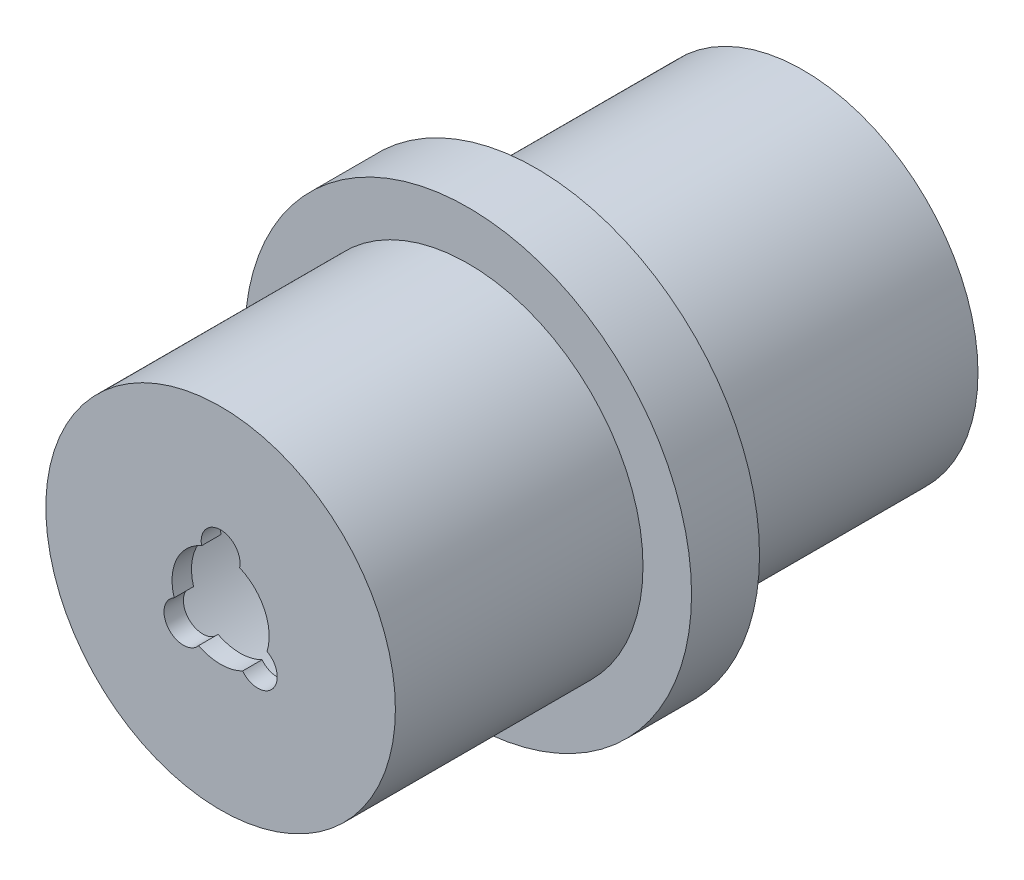
SolidWorks part; units mm, degrees
ref_plane "Front Plane" through (0, 0, 0) normal (0, 0, 1) x (1, 0, 0)
ref_plane "Top Plane" through (0, 0, 0) normal (0, 1, 0) x (1, 0, 0)
ref_plane "Right Plane" through (0, 0, 0) normal (1, 0, 0) x (0, 0, -1)
sketch "Sketch1" plane through (0, 0, 0) normal (1, 0, 0) x (0, 0, -1)
  line L0 (-60, 5) -> (-58, 5)
  line L1 (-60, 0) -> (0, 0)
  line L2 (-60, 0) -> (-60, 23)
  line L3 (-60, 23) -> (0, 23)
  line L4 (0, 0) -> (0, 23)
  line L5 (-1072.3815, 0) -> (1072.3815, 0) construction
  line L6 (-31, -974.342) -> (-31, 49025.6579)
  line L10 (-58, 0) -> (-2, 0)
  line L11 (-58, 0) -> (-58, 17)
  line L12 (-58, 17) -> (-2, 17)
  line L13 (-2, 0) -> (-2, 17)
  line L15 (-60, 18) -> (0, 18)
  line L16 (-27.5, 23) -> (-27.5, 18)
  line L17 (-2, 13) -> (0, 13)
  line L18 (-34.5, 23) -> (-34.5, 18)
  point P14 (-31, 17)
  dimension "D3" = 56
  dimension "D1" = 2
  dimension "D2" = 17
  dimension "D6" = 27
  dimension "D5" = 5
  dimension "D9" = 4
  dimension "D4" = 6
  dimension "D7" = 2
  dimension "D8" = 1
  dimension "D10" = 7
revolve "Revolve1" add sketch "Sketch1" angle 360 about L5 region at (0, 11.5, 59.6822) region at (0, 20.5, 32.75) region at (0, 17.5, 30.686) region at (0, 20.5, 29.25)
ref_axis "Axis1" through (0, 0, -68.4732) along (0, 0, 1)
ref_axis "Axis2" through (0, -974.342, 31) along (0, 1, 0)
ref_plane "Plane1" through (0, 0, 31) normal (0, 0, 1) x (1, 0, 0)
sketch "Sketch3" plane through (0, 0, 31) normal (0, 0, 1) x (1, 0, 0)
  line L0 (0, -999.5695) -> (0, 49000.4305) construction
  line L1 (-340.1578, -934.5758) -> (16760.8494, 46050.0552) construction
  line L2 (-1, 19.9725) -> (1, 19.9725)
  line L3 (338.8634, -931.0195) -> (-16762.1438, 46053.6116) construction
  line L4 (1, 19.9725) -> (4.5052, 16.5181) construction
  line L5 (0, 19.9725) -> (0, 23.1006) construction
  line L6 (2.0302, 19.9725) -> (-0.0328, 19.9725) construction
  line L7 (3.5107, 17.4982) -> (0.2868, 20.6753) construction
  line L8 (1, 19.9725) -> (1.1001, 21.9725) construction
  line L9 (4.5052, 16.5181) -> (4.684, 16.342)
  line L10 (6.4984, 17.8542) -> (7.5244, 20.6732)
  line L11 (-6.4984, 17.8542) -> (-7.5244, 20.6732)
  line L12 (-4.5052, 16.5181) -> (-4.684, 16.342)
  circle A4 centre (0, 0) radius 17 construction
  circle A6 centre (0, 0) radius 17
  circle A8 centre (5.2072, 17.2304) radius 1 construction
  arc A10 (6.4984, 17.8542) -> (-6.4984, 17.8542) centre (0, 0) cw
  circle A13 centre (0, 0) radius 22
  spline S0 degree 3 poles (1, 19.9725) (1.8375, 19.9725) (3.4007, 17.6066) (4.5052, 16.5181) knots 0 0 0 0 1 1 1 1
  spline S1 degree 3 poles (-1, 19.9725) (-1.8375, 19.9725) (-3.4007, 17.6066) (-4.5052, 16.5181) knots 0 0 0 0 1 1 1 1
  point P11 (0, 19.9725)
  point P13 (5.8143, 15.9748)
  point P16 (0, 22)
  point P20 (0, 19.9725)
  dimension "D2" = 2
  dimension "D4" = 20
  dimension "D1" = 5
  dimension "D3" = 1
  dimension "D5" = 2
  dimension "D6" = 2
extrude "Cut-Extrude1" cut sketch "Sketch3" against normal mid plane 4 contours L10 A13 L11 A10 S1 L2 S0 L9 A6 L12 region at (0, -18.441, 31)
extrude "Cut-Extrude2" cut sketch "Sketch3<5>" against normal mid plane 2 contours A6 | L2 S1 L12 A6 L9 S0 | L11 A13 L10 A10 region at (0, 18.1135, 31) region at (0, 0, 31) region at (7.5874, 19.0541, 31)
sketch "Sketch3<5>" plane through (0, 0, 31) normal (0, 0, 1) x (1, 0, 0) same geometry as "Sketch3"
ref_plane "Plane2" through (-7.5244, 20.6732, 32) normal (-0.9397, -0.342, 0) x (0, 0, 1)
sketch "Sketch5" plane through (0, 0, 60) normal (0, 0, 1) x (1, 0, 0)
  line L0 (3.8302, -3.2139) -> (-3.8302, -3.2139) construction
  circle A3 centre (0, 5) radius 2
  circle A4 centre (-3.8302, -3.2139) radius 2
  circle A5 centre (3.8302, -3.2139) radius 2
  circle A6 centre (0, 0) radius 5
  circle A7 centre (0, 0) radius 5 construction
  point P7 (0, -3.2139)
  point P9 (0, 0)
  point P10 (0, 0)
  point P11 (0, 0)
  circle M6 centre (0, 0) radius 5
extrude "Cut-Extrude3" cut sketch "Sketch5" against normal up to next contours A6 A4 M6 | A3 M6 | A6 A5 M6 region at (0, 5.7727, 60) region at (-4.4222, -3.7106, 60) region at (4.4222, -3.7106, 60)
equation "\"key_pin_length\"= 25.00mm"
equation "\"key_pin_dia\"= 20.00mm"
equation "\"driver_pin_travel\"= 3.00mm"
equation "\"driver_pin_dia\"= 0.3mm"
equation "\"plug_wall_thickness\" = 2mm"
equation "\"plug_spring_solid_length\"= 2mm"
equation "\"plug_length\"= 2 * \"key_pin_length\" + 2 * \"plug_wall_thickness\" + \"plug_spring_solid_length\""
equation "\"D3@Sketch1\"= \"plug_length\""
equation "\"D6@Sketch1\"= \"plug_wall_thickness\" + \"key_pin_length\""
equation "\"D7@Sketch1\"= \"D1@Sketch1\""
equation "\"driver_pin_head_dia\" = 2mm"
equation "\"D1@Sketch3\"=\"driver_pin_head_dia\"+\"driver_pin_travel\""
equation "\"true_gate_depth\" = 1.25mm"
equation "\"D4@Sketch1\"= \"driver_pin_head_dia\" + \"driver_pin_travel\" + 1mm"
equation "\"driver_pin_neck_dia\"= 2.00mm"
equation "\"driver_pin_head_length\" = 2mm"
equation "\"D1@Cut-Extrude1\"= \"driver_pin_neck_dia\" + \"driver_pin_head_length\""
equation "\"D1@Cut-Extrude2\"=\"driver_pin_neck_dia\""
equation "\"plug_dia\"= \"key_pin_dia\" + 2*(\"driver_pin_travel\" + 1mm + \"plug_spring_solid_length\" + 1mm)"
equation "\"D2@Sketch1\"=\"plug_dia\"/2"
equation "\"D2@Sketch3\"=\"driver_pin_head_dia\""
equation "\"D5@Sketch3\"=\"driver_pin_head_dia\""
equation "\"D6@Sketch3\"=\"driver_pin_head_dia\""
